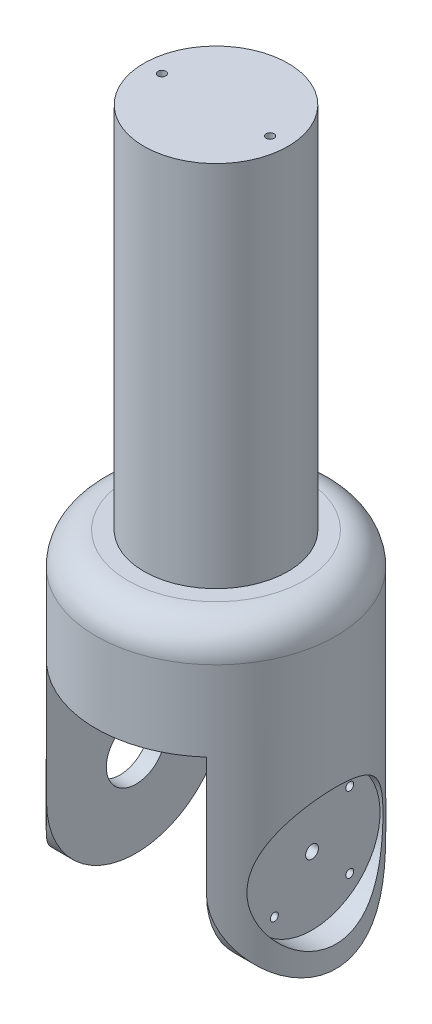
SolidWorks part; units mm, degrees
ref_plane "Front Plane" through (0, 0, 0) normal (0, 0, 1) x (1, 0, 0)
ref_plane "Top Plane" through (0, 0, 0) normal (0, 1, 0) x (1, 0, 0)
ref_plane "Right Plane" through (0, 0, 0) normal (1, 0, 0) x (0, 0, -1)
sketch "Sketch1" plane through (0, 0, 0) normal (0, 1, 0) x (1, 0, 0)
  circle A0 centre (0, 0) radius 75
  dimension "D1" = 150
extrude "Boss-Extrude1" add sketch "Sketch1" along normal blind 200
sketch "Sketch2" plane through (0, 0, 0) normal (0, -1, 0) x (1, 0, 0)
  line L0 (-50, -55.9017) -> (-50, 55.9017)
  line L1 (0, 0) -> (0, 109.4619) construction
  line L2 (50, -55.9017) -> (50, 55.9017)
  circle A2 centre (0, 0) radius 75 construction
  arc A3 (-50, -55.9017) -> (50, -55.9017) centre (0, 0) ccw
  circle A4 centre (0, 0) radius 75
  arc A5 (50, 55.9017) -> (-50, 55.9017) centre (0, 0) ccw
  dimension "D1" = 50
  dimension "D2" = 0
extrude "Cut-Extrude1" cut sketch "Sketch2" against normal blind 130
sketch "Sketch3" plane through (0, 200, 0) normal (0, 1, 0) x (1, 0, 0)
  circle A0 centre (0, 0) radius 45
  dimension "D1" = 90
extrude "Boss-Extrude2" add sketch "Sketch3" along normal blind 230
fillet "Fillet2" radius 20 1 edges at (0, 200, 75)
sketch "Sketch4" plane through (50, 0, 0) normal (-1, 0, 0) x (0, 0, 1)
  line L0 (-55.9017, 0) -> (55.9017, 0)
  line L1 (55.9017, 0) -> (55.9017, 55.9017)
  line L2 (-55.9017, 0) -> (-55.9017, 55.9017)
  arc A0 (-55.9017, 55.9017) -> (55.9017, 55.9017) centre (0, 55.9017) ccw
  line M1 (-55.9017, 0) -> (55.9017, 0)
  line M2 (55.9017, 0) -> (55.9017, 130)
  line M4 (-55.9017, 130) -> (-55.9017, 0)
extrude "Cut-Extrude2" cut sketch "Sketch4" along normal blind 230 and the other way blind 230 contours A0 L0 M2 | A0 M4 M1 region at (50, 12.4866, -43.4151) region at (50, 12.4866, 43.4151)
sketch "Sketch5" plane through (50, 0, 0) normal (-1, 0, 0) x (0, 0, 1)
  circle A0 centre (0, 55.9017) radius 42.5
  dimension "D1" = 85
extrude "Cut-Extrude3" cut sketch "Sketch5" against normal blind 20 from offset 10 offset against normal yes
sketch "Sketch6" plane through (-50, 0, 0) normal (1, 0, 0) x (0, 0, -1)
  circle A0 centre (0, 55.9017) radius 40
  dimension "D1" = 80
extrude "Cut-Extrude4" cut sketch "Sketch6" against normal blind 20 from offset 10 offset against normal yes
sketch "Sketch7" plane through (-60, 0, 0) normal (-1, 0, 0) x (0, 0, 1)
  circle A0 centre (0, 55.9017) radius 16
  dimension "D1" = 32
extrude "Cut-Extrude5" cut sketch "Sketch7" against normal blind 20
sketch "Sketch8" plane through (60, 0, 0) normal (1, 0, 0) x (0, 0, -1)
  circle A0 centre (0, 55.9017) radius 4
  dimension "D1" = 8
extrude "Cut-Extrude6" cut sketch "Sketch8" against normal blind 20
sketch "Sketch9" plane through (-60, 0, 0) normal (-1, 0, 0) x (0, 0, 1)
  circle A0 centre (0, 55.9017) radius 18.5
  dimension "D1" = 37
extrude "Cut-Extrude7" cut sketch "Sketch9" against normal blind 40
sketch "Sketch10" plane through (60, 0, 0) normal (1, 0, 0) x (0, 0, -1)
  circle A0 centre (-23.55, 32.3517) radius 2.5
  circle A1 centre (23.55, 32.3517) radius 2.5
  circle A2 centre (23.55, 79.4517) radius 2.5
  circle A3 centre (-23.55, 79.4517) radius 2.5
extrude "Cut-Extrude8" cut sketch "Sketch10" against normal blind 40
sketch "Sketch11" plane through (0, 440, 0) normal (0, 1, 0) x (1, 0, 0)
  circle A0 centre (-33.7662, 0) radius 2.5
  circle A1 centre (33.7662, 0) radius 2.5
extrude "Cut-Extrude9" cut sketch "Sketch11" against normal blind 40
sketch "Sketch12" plane through (0, 0, 0) normal (1, 0, 0) x (0, 0, -1)
  point P0 (0, 55.9017)
